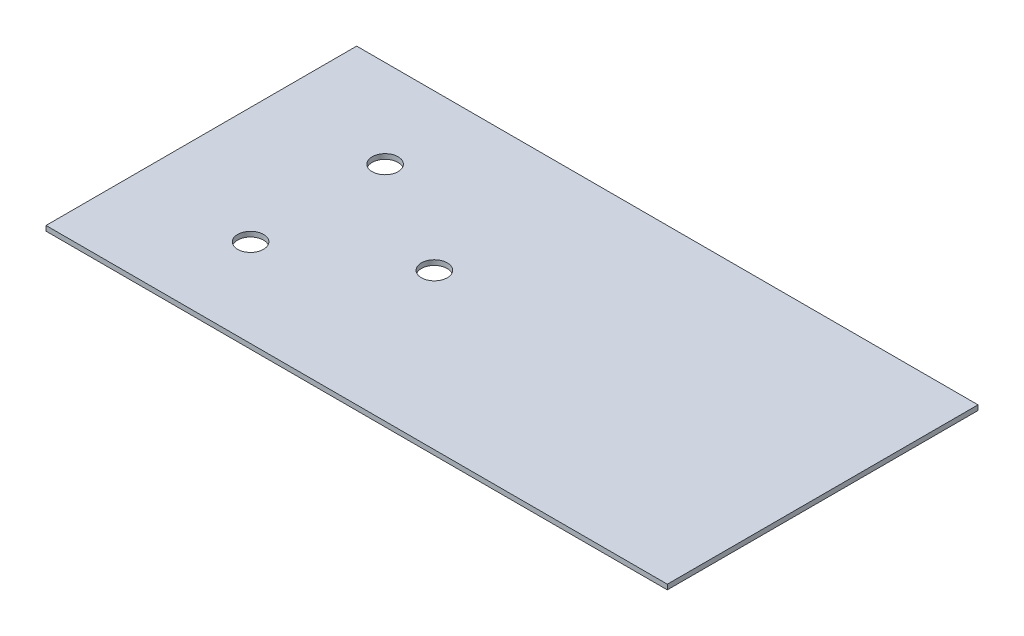
SolidWorks part; units mm, degrees
note: '?' marks a value the reader was unsure of.
ref_plane "Front Plane" through (0, 0, 0) normal (0, 0, 1) x (1, 0, 0)
ref_plane "Top Plane" through (0, 0, 0) normal (0, 1, 0) x (1, 0, 0)
ref_plane "Right Plane" through (0, 0, 0) normal (1, 0, 0) x (0, 0, -1)
sketch "Sketch2" plane through (0, 0, 0) normal (0, 1, 0) x (1, 0, 0)
  line L0 (0, 76.2) -> (0, 0)
  line L1 (0, 0) -> (152.4, 0)
  line L2 (152.4, 0) -> (152.4, 76.2)
  line L3 (152.4, 76.2) -> (0, 76.2)
  line L4 (0, -55) -> (0, 55) construction
  line L5 (-55, 0) -> (55, 0) construction
  dimension "D1" = 76.2
  dimension "D2" = 152.4
base flange "Base-Flange1" sketch "Sketch2" thickness 1.2192 reverse thickness direction yes parameters "D1"=0.7366
sketch "Sketch7" plane through (0, 1.2192, 0) normal (0, 1, 0) x (1, 0, 0)
  line L0 (0, 0) -> (76.2, 76.2) construction
  line L1 (152.4, 76.2) -> (0, 76.2) construction
  line L2 (76.2, 76.2) -> (0, 76.2) construction
  line L3 (38.1, 38.1) -> (63.5, 38.1) construction
  line L4 (0, 0) -> (152.4, 0) construction
  circle A0 centre (38.1, 38.1) radius 19.05
  dimension "D2" = 19.05
  dimension "D1" = 76.2
  dimension "D3" = 25.4
hole_wizard "1/4 (0.25) Diameter Hole1" positions "3DSketch1" profile "Sketch8" hole size "1/4" standard "ANSI Inch" end condition through all
sketch3d "3DSketch1"
  line L0 (38.1, 1.2192, -38.1) -> (63.5, 1.2192, -38.1) construction
  circle A0 centre (38.1, 1.2192, -38.1) radius 19.05 construction
  point P0 (57.15, 1.2192, -38.1)
  point P5 (38.1, 20.2692, -38.1)
sketch "Sketch8" plane through (57.15, 1.2192, -38.1) normal (1, 0, 0) x (0, 0, 1)
  line L0 (0, 0) -> (0, 1.2192)
  line L1 (0, 1.2192) -> (3.175, 1.2192)
  line L2 (3.175, 1.2192) -> (3.175, 0)
  line L5 (3.175, 0) -> (0, 0)
  line L11 (0, -6.35) -> (0, 107.95) construction
  dimension "Thru Hole Dia." = 6.35
  dimension "Thru Hole Depth" = 1.2192
ref_axis "Axis1" through (38.1, 1.2192, -38.1) along (0, 1, 0)?
pattern_circular "CirPattern1" count 3 over 360 about axis through (38.1, 0, -38.1) along (0, 1, 0) of "1/4 (0.25) Diameter Hole1"
sketch "Bend-Lines1" [suppressed] plane through (0, 0, 0) normal (0, 1, 0) x (1, 0, 0)
sketch "Bounding-Box1" [suppressed] plane through (0, 0, 0) normal (0, 1, 0) x (1, 0, 0)
sheet metal parameters "Sheet-Metal1" thickness 1.2192 parameters "D1"=0.7366
flat pattern "Flat-Pattern1" [suppressed]
sketch "Bend-Lines2" plane through (0, 0, 0) normal (0, 1, 0) x (1, 0, 0)
sketch3d "Bounding-Box2" [suppressed]
  line L0 (-152.4, 0, 0) -> (0, 0, 0) construction
  line L1 (-152.4, 76.2, 0) -> (0, 76.2, 0) construction
  line L2 (-152.4, 0, 0) -> (-152.4, 76.2, 0) construction
  line L3 (0, 0, 0) -> (0, 76.2, 0) construction
sheet metal parameters "Sheet-Metal2" thickness 1.2192 parameters "D1"=0.7366
flat pattern "Flat-Pattern1" [suppressed]
sketch "Bend-Lines2" plane through (0, 0, 0) normal (0, 1, 0) x (1, 0, 0)
sketch3d "Bounding-Box2" [suppressed]
  line L0 (-152.4, 0, 0) -> (0, 0, 0) construction
  line L1 (-152.4, 76.2, 0) -> (0, 76.2, 0) construction
  line L2 (-152.4, 0, 0) -> (-152.4, 76.2, 0) construction
  line L3 (0, 0, 0) -> (0, 76.2, 0) construction
sketch "Sketch7-1" [suppressed] plane through (0, 0.889, 0) normal (0, 1, 0) x (1, 0, 0)
  line L0 (0, 0) -> (76.2, 76.2) construction
  line L2 (76.2, 76.2) -> (0, 76.2) construction
  line L3 (38.1, 38.1) -> (63.5, 38.1) construction
  circle A0 centre (38.1, 38.1) radius 12.7
  dimension "D2" = 12.7
  dimension "D1" = 76.2
  dimension "D3" = 25.4
sketch "Sketch7-2" [suppressed] plane through (0, 0.889, 0) normal (0, 1, 0) x (1, 0, 0)
  line L0 (0, 0) -> (76.2, 76.2) construction
  line L2 (76.2, 76.2) -> (0, 76.2) construction
  line L3 (38.1, 38.1) -> (63.5, 38.1) construction
  circle A0 centre (38.1, 38.1) radius 12.7
  dimension "D2" = 12.7
  dimension "D1" = 76.2
  dimension "D3" = 25.4
sheet metal parameters "Sheet-Metal3" thickness 1.2192 parameters "D1"=0.7366
flat pattern "Flat-Pattern1" [suppressed]
sketch "Bend-Lines2" plane through (0, 0, 0) normal (0, 1, 0) x (1, 0, 0)
sketch3d "Bounding-Box2" [suppressed]
  line L0 (-152.4, 0, 0) -> (0, 0, 0) construction
  line L1 (-152.4, 76.2, 0) -> (0, 76.2, 0) construction
  line L2 (-152.4, 0, 0) -> (-152.4, 76.2, 0) construction
  line L3 (0, 0, 0) -> (0, 76.2, 0) construction
sketch "Sketch7-1" plane through (0, 1.2192, 0) normal (0, 1, 0) x (1, 0, 0)
  line L0 (0, 0) -> (76.2, 76.2) construction
  line L2 (76.2, 76.2) -> (0, 76.2) construction
  line L3 (38.1, 38.1) -> (63.5, 38.1) construction
  circle A0 centre (38.1, 38.1) radius 19.05
  dimension "D2" = 19.05
  dimension "D1" = 76.2
  dimension "D3" = 25.4
sketch "Sketch7-2" [suppressed] plane through (0, 0.889, 0) normal (0, 1, 0) x (1, 0, 0)
  line L0 (0, 0) -> (76.2, 76.2) construction
  line L2 (76.2, 76.2) -> (0, 76.2) construction
  line L3 (38.1, 38.1) -> (63.5, 38.1) construction
  circle A0 centre (38.1, 38.1) radius 12.7
  dimension "D2" = 12.7
  dimension "D1" = 76.2
  dimension "D3" = 25.4
sketch "Sketch7-3" [suppressed] plane through (0, 0.889, 0) normal (0, 1, 0) x (1, 0, 0)
  line L0 (0, 0) -> (76.2, 76.2) construction
  line L2 (76.2, 76.2) -> (0, 76.2) construction
  line L3 (38.1, 38.1) -> (63.5, 38.1) construction
  circle A0 centre (38.1, 38.1) radius 12.7
  dimension "D2" = 12.7
  dimension "D1" = 76.2
  dimension "D3" = 25.4
sketch "Sketch7-4" plane through (0, 0.889, 0) normal (0, 1, 0) x (1, 0, 0)
  line L0 (0, 0) -> (76.2, 76.2) construction
  line L2 (76.2, 76.2) -> (0, 76.2) construction
  line L3 (38.1, 38.1) -> (63.5, 38.1) construction
  circle A0 centre (38.1, 38.1) radius 19.05
  dimension "D2" = 19.05
  dimension "D1" = 76.2
  dimension "D3" = 25.4
sketch "Sketch7-5" plane through (0, 1.2192, 0) normal (0, 1, 0) x (1, 0, 0)
  line L0 (0, 0) -> (76.2, 76.2) construction
  line L2 (76.2, 76.2) -> (0, 76.2) construction
  line L3 (38.1, 38.1) -> (63.5, 38.1) construction
  circle A0 centre (38.1, 38.1) radius 19.05
  dimension "D2" = 19.05
  dimension "D1" = 76.2
  dimension "D3" = 25.4
sketch "Sketch7-6" plane through (0, 1.2192, 0) normal (0, 1, 0) x (1, 0, 0)
  line L0 (0, 0) -> (76.2, 76.2) construction
  line L2 (76.2, 76.2) -> (0, 76.2) construction
  line L3 (38.1, 38.1) -> (63.5, 38.1) construction
  circle A0 centre (38.1, 38.1) radius 19.05
  dimension "D2" = 19.05
  dimension "D1" = 76.2
  dimension "D3" = 25.4
